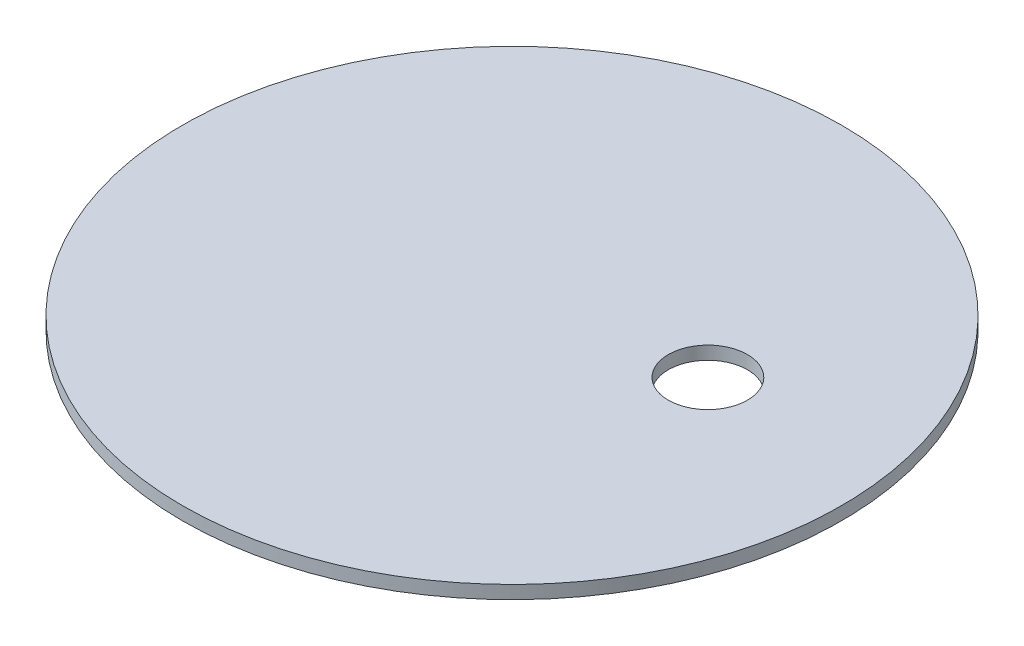
SolidWorks part; units mm, degrees
ref_plane "Front Plane" through (0, 0, 0) normal (0, 0, 1) x (1, 0, 0)
ref_plane "Top Plane" through (0, 0, 0) normal (0, 1, 0) x (1, 0, 0)
ref_plane "Right Plane" through (0, 0, 0) normal (1, 0, 0) x (0, 0, -1)
sketch "Sketch13" plane through (0, 0, 0) normal (0, 1, 0) x (1, 0, 0)
  circle A0 centre (-23, -6.7193) radius 50
extrude "Boss-Extrude6" add sketch "Sketch13" along normal blind 2 contours A0
sketch "Sketch15" plane through (0, 2, 0) normal (0, 1, 0) x (1, 0, 0)
  circle A0 centre (0, 0) radius 6 construction
  circle A1 centre (0, 0) radius 6
extrude "Cut-Extrude5" cut sketch "Sketch15" against normal through all
sketch "Sketch16" plane through (0, 2, 0) normal (0, 1, 0) x (1, 0, 0)
  line L4 (-20, -61.23) -> (-20, -48.33)
  line L5 (-20, -48.33) -> (-25.9, -48.33)
  line L6 (-25.9, -48.33) -> (-25.9, -61.23)
  line L7 (-25.9, -61.23) -> (-20, -61.23)
  line L8 (-20, -61.23) -> (-20, -48.33)
  line L9 (-20, -48.33) -> (-25.9, -48.33)
  line L10 (-25.9, -48.33) -> (-25.9, -61.23)
  line L11 (-25.9, -61.23) -> (-20, -61.23)
  dimension "D1" = 0
extrude "Boss-Extrude7" [suppressed] add sketch "Sketch16" against normal blind 2
sketch "Sketch17" [suppressed] plane through (0, 2, 0) normal (0, 1, 0) x (1, 0, 0)
  line L1 (-25.9, -64.6351) -> (-13.9, -64.6351)
  line L2 (-25.9, -64.6351) -> (-25.9, -56.6351)
  line L3 (-25.9, -56.6351) -> (-13.9, -56.6351)
  line L4 (-13.9, -64.6351) -> (-13.9, -56.6351)
  line L5 (-20, -56.6292) -> (-32, -56.6292)
  line L6 (-20, -56.6292) -> (-20, -64.6351)
  line L7 (-20, -64.6351) -> (-32, -64.6351)
  line L8 (-32, -56.6292) -> (-32, -64.6351)
  arc M3 (-20, -56.6292) -> (-25.9, -56.6351) centre (-23, -6.7193) ccw
  line M4 (-25.9, -56.6351) -> (-25.9, -61.23)
  line M5 (-25.9, -61.23) -> (-20, -61.23)
  line M6 (-20, -61.23) -> (-20, -56.6292)
  dimension "D1" = 12
  dimension "D2" = 8
extrude "Boss-Extrude8" [suppressed] add sketch "Sketch17" against normal blind 2 contours L6 L1 L4 L3 M6 | L6 L2 L1 M5 | L5 L8 L7 L2 M4 M3
sketch "Sketch18" [suppressed] plane through (0, 2, 0) normal (0, 1, 0) x (1, 0, 0)
  line L0 (-32, -56.6292) -> (-32, -55.9026)
  line L1 (-32, -55.9026) -> (-26, -56.6292)
  line L2 (-26, -56.6292) -> (-32, -56.6292) construction
  line L3 (-26, -56.6292) -> (-32, -56.6292)
  line L4 (-13.9, -56.6351) -> (-13.9, -55.8842)
  line L5 (-13.9, -55.8842) -> (-20, -56.6351)
  line L6 (-20, -56.6351) -> (-13.9, -56.6351)
  arc A0 (-20, -56.6292) -> (-26, -56.6292) centre (-23, -6.7193) ccw construction
extrude "Boss-Extrude9" [suppressed] add sketch "Sketch18" against normal blind 2
